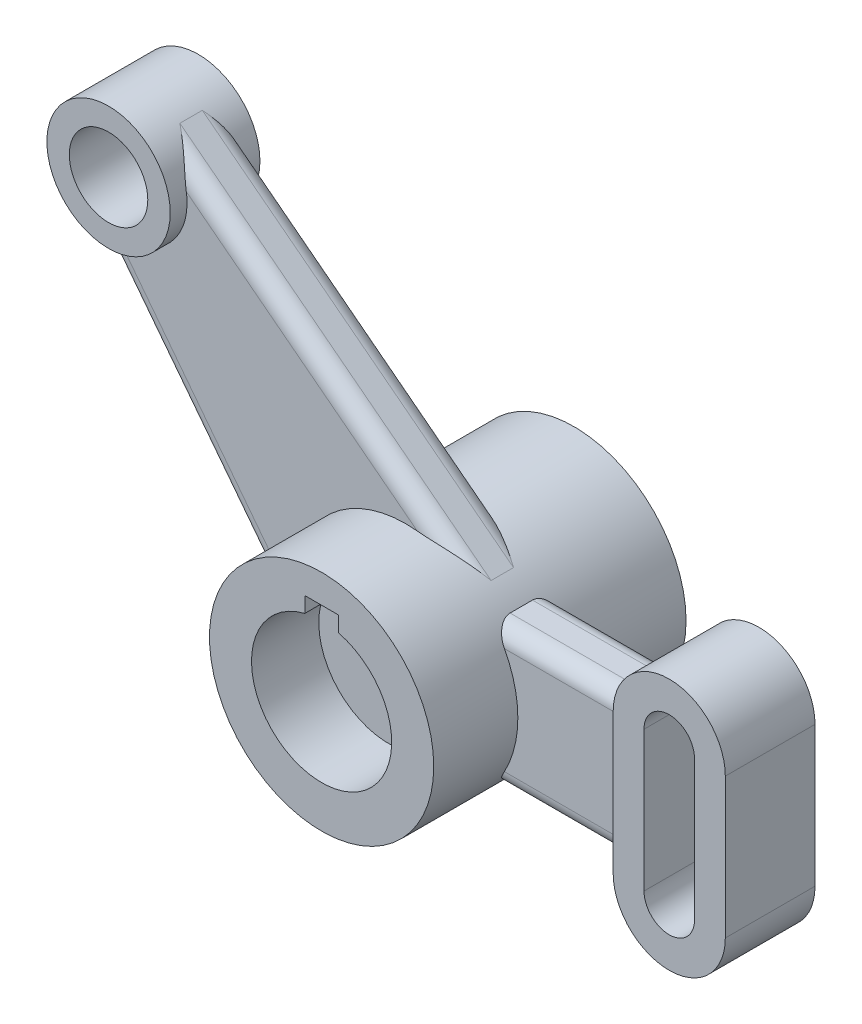
SolidWorks part; units mm, degrees
ref_plane "Ebene vorne" through (0, 0, 0) normal (0, 0, 1) x (1, 0, 0)
ref_plane "Ebene oben" through (0, 0, 0) normal (0, 1, 0) x (1, 0, 0)
ref_plane "Ebene rechts" through (0, 0, 0) normal (1, 0, 0) x (0, 0, -1)
sketch "Sketch1" plane through (0, 0, 0) normal (0, 0, 1) x (1, 0, 0)
  line L0 (0, 0) -> (-50, 0) construction
  line L1 (-50, 0) -> (-100, 50) construction
  line L2 (0, -12.5) -> (0, 12.5) construction
  line L3 (-10, -12.5) -> (-10, 12.5)
  line L4 (10, -12.5) -> (10, 12.5)
  line L5 (0, -12.5) -> (0, 12.5) construction
  line L6 (-4.5, -12.5) -> (-4.5, 12.5)
  line L7 (4.5, -12.5) -> (4.5, 12.5)
  line L8 (-10, 12.5) -> (-34.3875, 12.5)
  line L9 (-10, -12.5) -> (-34.3875, -12.5)
  line L10 (-93.2751, 58.7049) -> (-37.7729, 15.8271)
  line L11 (-108.7049, 43.2751) -> (-65.8271, -12.2271)
  line L12 (-50, 0) -> (-50, 20) construction
  line L13 (-53, 14.9) -> (-47, 14.9)
  line L14 (-47, 14.9) -> (-47, 12.1347)
  line L15 (-53, 14.9) -> (-53, 12.1347)
  circle A0 centre (-100, 50) radius 7
  circle A1 centre (-100, 50) radius 11
  circle A2 centre (-50, 0) radius 20
  arc A3 (-53, 12.1347) -> (-47, 12.1347) centre (-50, 0) ccw
  arc A4 (-10, -12.5) -> (10, -12.5) centre (0, -12.5) ccw
  arc A5 (10, 12.5) -> (-10, 12.5) centre (0, 12.5) ccw
  arc A6 (-4.5, -12.5) -> (4.5, -12.5) centre (0, -12.5) ccw
  arc A7 (4.5, 12.5) -> (-4.5, 12.5) centre (0, 12.5) ccw
  point P8 (0, 0)
  point P15 (0, 0)
  point P35 (-50, 12.5)
  dimension "D1" = 25
  dimension "D2" = 10
  dimension "D3" = 4.5
  dimension "D4" = 40
  dimension "D8" = 25
  dimension "D9" = 22
  dimension "D10" = 14
  dimension "D5" = 50
  dimension "D6" = 100
  dimension "D7" = 45
  dimension "D11" = 6
  dimension "D12" = 2.4
extrude "Boss-Extrude1" add sketch "Sketch1" along normal mid plane 10 contours A2 L9 L3 L8 | A2 L10 A1 L11 region at (-20.7343, 0, 0) region at (-76.7785, 26.7785, 0)
extrude "Boss-Extrude2" add sketch "Sketch1<3>" along normal mid plane 16 contours L4 A5 L3 A4 A7 L7 A6 L6 region at (-9.5076, 0, 0)
sketch "Sketch1<3>" plane through (0, 0, 0) normal (0, 0, 1) x (1, 0, 0) same geometry as "Sketch1"
extrude "Boss-Extrude3" add sketch "Sketch1<4>" along normal mid plane 16 contours A1 A0 region at (-107.5582, 57.5582, 0)
sketch "Sketch1<4>" plane through (0, 0, 0) normal (0, 0, 1) x (1, 0, 0) same geometry as "Sketch1"
extrude "Boss-Extrude4" add sketch "Sketch1<5>" along normal blind 20 and the other way blind 25 contours A2
sketch "Sketch1<5>" plane through (0, 0, 0) normal (0, 0, 1) x (1, 0, 0) same geometry as "Sketch1"
extrude "Cut-Extrude1" cut sketch "Sketch1<7>" along normal up to surface (20 mm away) from offset 8 contours A3 L14 L13 L15 up to face at (-30, 0, 20)
sketch "Sketch1<7>" plane through (0, 0, 0) normal (0, 0, 1) x (1, 0, 0) same geometry as "Sketch1"
fillet "Fillet2" radius 3 8 edges at (-22.1938, -12.5, 5) (-22.1938, -12.5, -5) (-22.1938, 12.5, 5) (-22.1938, 12.5, -5) (-87.266, 15.524, -5) (-87.266, 15.524, 5) (-65.524, 37.266, -5) (-65.524, 37.266, 5)
sketch "Sketch2" plane through (0, 0, -25) normal (0, 0, -1) x (-1, 0, 0)
  line L11 (47, 14.9) -> (47, 12.1347)
  line L12 (53, 14.9) -> (47, 14.9)
  line L13 (53, 12.1347) -> (53, 14.9)
  line L14 (47, 14.9) -> (47, 12.1347)
  line L15 (53, 14.9) -> (47, 14.9)
  line L16 (53, 12.1347) -> (53, 14.9)
  arc A7 (47, 12.1347) -> (53, 12.1347) centre (50, 0) ccw
  arc A16 (47, 12.1347) -> (53, 12.1347) centre (50, 0) ccw
  dimension "D6" = 0
extrude "Cut-Extrude2" cut sketch "Sketch2" against normal blind 13
